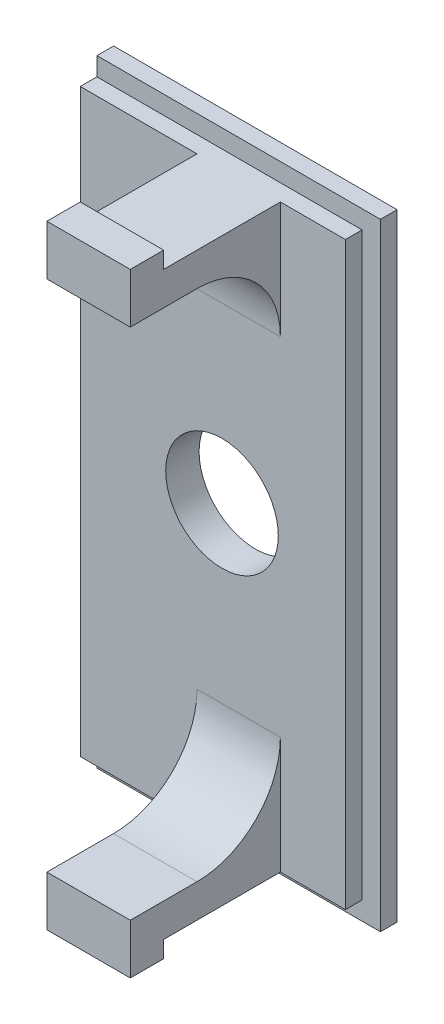
SolidWorks part; units mm, degrees
ref_plane "Plan de face" through (0, 0, 0) normal (0, 0, 1) x (1, 0, 0)
ref_plane "Plan de dessus" through (0, 0, 0) normal (0, 1, 0) x (1, 0, 0)
ref_plane "Plan de droite" through (0, 0, 0) normal (1, 0, 0) x (0, 0, -1)
sketch "Esquisse1" plane through (0, 0, 0) normal (0, 0, 1) x (1, 0, 0)
  line L1 (-17, 37) -> (17, 37)
  line L2 (-17, 37) -> (-17, -37)
  line L3 (-17, -37) -> (17, -37)
  line L4 (17, 37) -> (17, -37)
  point P4 (0, 37)
  point P6 (-17, 0)
  dimension "D1" = 34
  dimension "D2" = 74
extrude "Boss.-Extru.1" add sketch "Esquisse1" along normal blind 2
sketch "Esquisse2" plane through (0, 0, 2) normal (0, 0, 1) x (1, 0, 0)
  line L0 (-17, 37) -> (-17, -37) construction
  line L1 (-17, 34.8) -> (14.8, 34.8)
  line L2 (-17, 34.8) -> (-17, -34.8)
  line L3 (-17, -34.8) -> (14.8, -34.8)
  line L4 (14.8, 34.8) -> (14.8, -34.8)
  line L5 (17, 37) -> (-17, 37) construction
  line L6 (17, -37) -> (17, 37) construction
  line L7 (-17, -37) -> (17, -37) construction
  dimension "D1" = 2.2
  dimension "D2" = 2.2
  dimension "D3" = 2.2
extrude "Boss.-Extru.2" add sketch "Esquisse2" along normal blind 2
sketch "Esquisse7" plane through (0, 0, 4) normal (0, 0, 1) x (1, 0, 0)
  line L0 (14.8, 34.8) -> (-17, 34.8) construction
  line L1 (-3, 34.8) -> (7, 34.8)
  line L2 (-3, 34.8) -> (-3, 30.8)
  line L3 (-3, 30.8) -> (7, 30.8)
  line L4 (7, 34.8) -> (7, 30.8)
  line L5 (-17, -34.8) -> (14.8, -34.8) construction
  line L6 (-3, -34.8) -> (7, -34.8)
  line L7 (-3, -34.8) -> (-3, -30.8)
  line L8 (-3, -30.8) -> (7, -30.8)
  line L9 (7, -34.8) -> (7, -30.8)
  line L10 (17, -37) -> (17, 37) construction
  dimension "D1" = 4
  dimension "D2" = 10
  dimension "D3" = 10
extrude "Boss.-Extru.5" add sketch "Esquisse7" along normal blind 18
sketch "Esquisse8" plane through (0, 0, 22) normal (0, 0, 1) x (1, 0, 0)
  line L1 (7, 30.8) -> (7, 34.8) construction
  line L2 (-3, 34.8) -> (7, 34.8)
  line L3 (-3, 34.8) -> (-3, 36.8)
  line L4 (-3, 36.8) -> (7, 36.8)
  line L5 (7, -34.8) -> (7, -30.8) construction
  line L6 (-3, -34.8) -> (7, -34.8)
  line L7 (-3, -34.8) -> (-3, -36.8)
  line L8 (-3, -36.8) -> (7, -36.8)
  line L10 (7, -34.8) -> (7, -36.8)
  line L11 (7, 34.8) -> (7, 36.8)
  dimension "D1" = 2
extrude "Boss.-Extru.6" add sketch "Esquisse8" against normal blind 4
fillet "Congé2" radius 10 2 edges at (2, 30.8, 4) (2, -30.8, 4)
sketch "Sketch1" plane through (0, 0, 0) normal (0, 0, -1) x (-1, 0, 0)
  circle A0 centre (0, 0) radius 6.75
  dimension "D1" = 13.5
extrude "Cut-Extrude1" cut sketch "Sketch1" against normal through all
